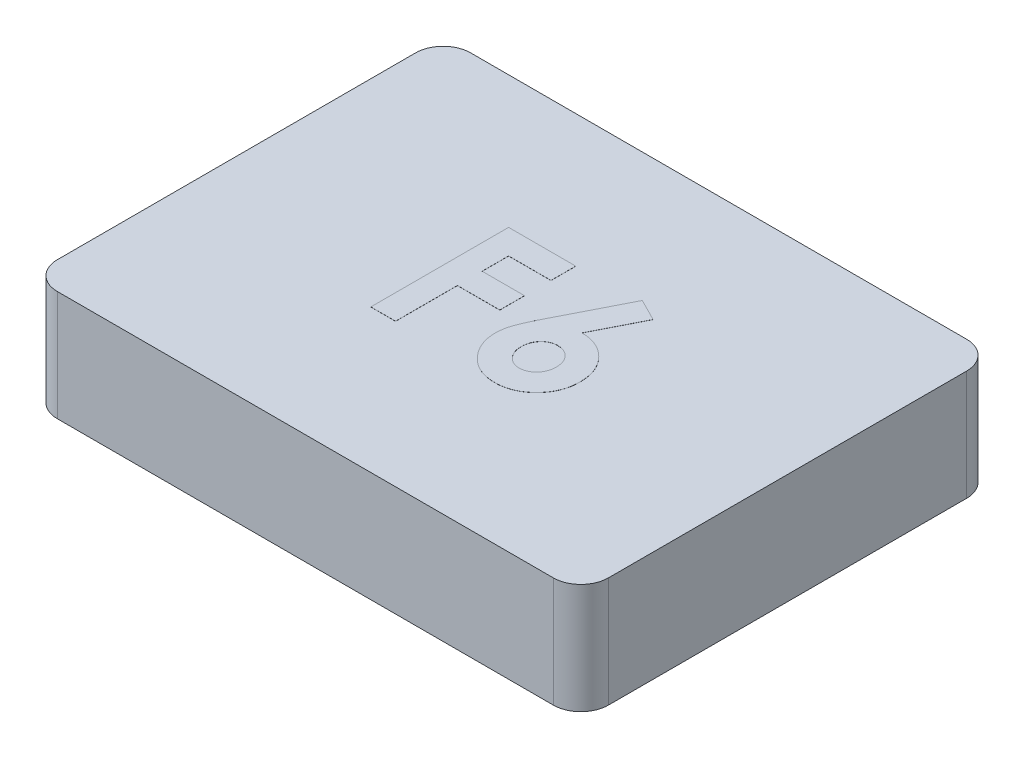
SolidWorks part; units mm, degrees
ref_plane "Front Plane" through (0, 0, 0) normal (0, 0, 1) x (1, 0, 0)
ref_plane "Top Plane" through (0, 0, 0) normal (0, 1, 0) x (1, 0, 0)
ref_plane "Right Plane" through (0, 0, 0) normal (1, 0, 0) x (0, 0, -1)
sketch "Sketch1" plane through (0, 0, 0) normal (0, 1, 0) x (1, 0, 0)
  line L0 (0, 0) -> (12.7, 0)
  line L1 (12.7, 0) -> (12.7, 9.525)
  line L2 (12.7, 9.525) -> (0, 9.525)
  line L3 (0, 9.525) -> (0, 0)
  dimension "D1" = 12.7
  dimension "D2" = 9.525
extrude "Boss-Extrude1" add sketch "Sketch1" along normal blind 2.54
fillet "Fillet1" radius 0.635 4 edges at (0, 1.27, -9.525) (12.7, 1.27, -9.525) (12.7, 1.27, 0) (0, 1.27, 0)
shell "Shell1" thickness 0.635 removed face at (6.35, 0, -4.7625)
sketch "Sketch2" plane through (0, 1.905, 0) normal (0, -1, 0) x (-1, 0, 0)
  line L0 (-0.635, 4.7625) -> (-12.065, 4.7625) construction
  line L1 (-0.635, 8.89) -> (-0.635, 0.635) construction
  line L2 (-12.065, 0.635) -> (-12.065, 8.89) construction
  line L3 (-6.35, 0.635) -> (-6.35, 8.89) construction
  line L4 (-0.635, 0.635) -> (-12.065, 0.635) construction
  line L5 (-12.065, 8.89) -> (-0.635, 8.89) construction
  circle A0 centre (-6.35, 4.7625) radius 2.54
  dimension "D1" = 5.08
extrude "Boss-Extrude2" add sketch "Sketch2" along normal up to surface (1.905 mm away) up to face at (6.35, 0, -4.7625)
sketch "Sketch3" plane through (0, 2.54, 0) normal (0, 1, 0) x (1, 0, 0)
  line L0 (0.635, 0) -> (12.065, 0) construction
  line L1 (0, 8.89) -> (0, 0.635) construction
  text T0 "<b>F6</b>"
  dimension "D1" = 3.302
  dimension "D2" = 4.191
extrude "Boss-Extrude3" add sketch "Sketch3" along normal blind 0.0025
